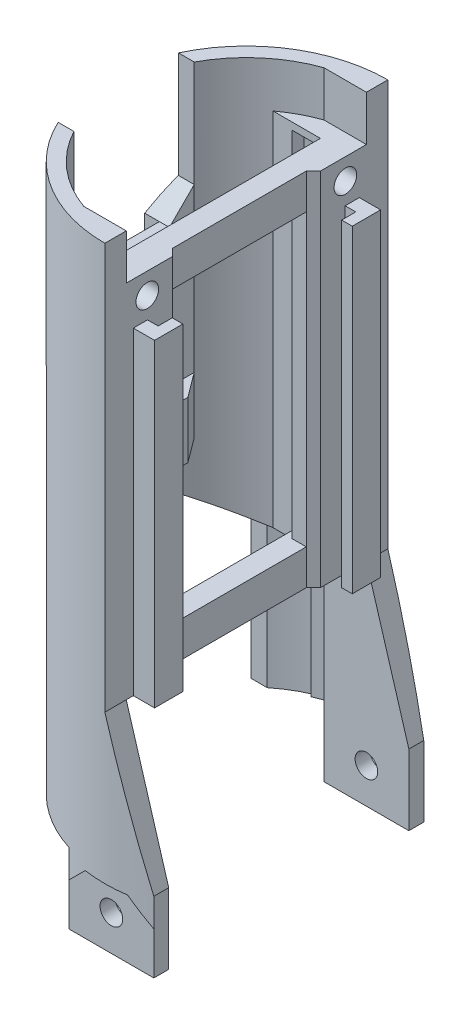
SolidWorks part; units mm, degrees
ref_plane "前视基准面" through (0, 0, 0) normal (0, 0, 1) x (1, 0, 0)
ref_plane "上视基准面" through (0, 0, 0) normal (0, 1, 0) x (1, 0, 0)
ref_plane "右视基准面" through (0, 0, 0) normal (1, 0, 0) x (0, 0, -1)
other "Configuration Table"
sketch "草图1" plane through (0, 0, 0) normal (0, 1, 0) x (1, 0, 0)
  line L0 (0, -473.638) -> (0, 23208.2609) construction
  line L1 (0, 0) -> (-4, 0) construction
  line L2 (0, 20) -> (0, -20)
  line L3 (-4, -17.5499) -> (-4, 17.5499)
  arc A0 (0, 20) -> (0, -20) centre (0, 0) ccw
  arc A1 (-4, 17.5499) -> (-4, -17.5499) centre (0, 0) ccw
  point P12 (-4, 0)
  dimension "D1" = 40
  dimension "D2" = 36
  dimension "D3" = 4
extrude "凸台-拉伸1" add sketch "草图1" along normal blind 70
sketch "草图3" plane through (0, 0, 0) normal (1, 0, 0) x (0, 0, -1)
  line L0 (-20, 0) -> (20, 0) construction
  line L1 (-16, 60) -> (16, 60) construction
  line L2 (-16, 60) -> (-16, 0) construction
  line L3 (-16, 0) -> (16, 0) construction
  line L4 (16, 60) -> (16, 0) construction
  line L5 (-20, 70) -> (20, 70) construction
  circle A0 centre (-14, 58) radius 2 construction
  circle A1 centre (14, 58) radius 2 construction
  circle A2 centre (-14, 58) radius 1
  circle A3 centre (14, 58) radius 1
  point P4 (0, 60)
  dimension "D4" = 4
  dimension "D5" = 4
  dimension "D6" = 2
  dimension "D7" = 2
  dimension "D1" = 0
  dimension "D2" = 10
  dimension "D3" = 32
extrude "切除-拉伸2" cut sketch "草图3" against normal up to surface (4 mm away) from surface up to face at (-4, 35, 0) starting at face at (0, 35, 0)
sketch "草图5" plane through (0, 0, 0) normal (0, 1, 0) x (1, 0, 0)
  line L0 (0, -1000) -> (0, 49000) construction
  line L1 (-1000, 0) -> (49000, 0) construction
  line L2 (-6, 16.9706) -> (6, 16.9706) construction
  line L3 (-6, -16.9706) -> (6, -16.9706) construction
  line L4 (0, 16.9706) -> (0, -16.9706)
  line L5 (0, -16.9706) -> (-4, -16.9706)
  line L6 (-4, -17.5499) -> (-4, 17.5499) construction
  line L7 (-4, -16.9706) -> (-4, 16.9706)
  line L8 (-4, 16.9706) -> (0, 16.9706)
  circle A0 centre (0, 0) radius 18 construction
  point P11 (0, 16.9706)
  dimension "D1" = 12
extrude "切除-拉伸4" cut sketch "草图5" against normal blind 9 from surface starting at face at (-10, 70, 0)
sketch "草图6" plane through (0, 0, 0) normal (0, 1, 0) x (1, 0, 0)
  line L0 (-4, 16.9706) -> (-6, 16.9706)
  line L1 (0, 16.9706) -> (0, 18)
  line L2 (-4, -16.9706) -> (-6, -16.9706)
  line L3 (0, -16.9706) -> (0, -18)
  line L4 (-4, 16.9706) -> (-4, -16.9706)
  line L5 (0, 16.9706) -> (-4, 16.9706)
  line L6 (0, -16.9706) -> (0, 16.9706)
  line L7 (-4, -16.9706) -> (0, -16.9706)
  line L9 (0, 16.9706) -> (-4, 16.9706)
  line L11 (-4, -16.9706) -> (0, -16.9706)
  arc A0 (0, 18) -> (-6, 16.9706) centre (0, 0) ccw
  arc A1 (-6, -16.9706) -> (0, -18) centre (0, 0) ccw
  dimension "D1" = 0
extrude "凸台-拉伸2" add sketch "草图6" against normal up to surface from surface up to face at (-10, 0, 0) starting at face at (-6.25, 70, 0)
sketch "草图7" plane through (0, 0, 0) normal (0, 1, 0) x (1, 0, 0)
  line L4 (-4, 16.9706) -> (-4, -16.9706)
  line L5 (0, 16.9706) -> (-4, 16.9706)
  line L6 (0, -16.9706) -> (0, 16.9706)
  line L7 (-4, -16.9706) -> (0, -16.9706)
  line L8 (-4, 16.9706) -> (-4, -16.9706)
  line L9 (0, 16.9706) -> (-4, 16.9706)
  line L10 (0, -16.9706) -> (0, 16.9706)
  line L11 (-4, -16.9706) -> (0, -16.9706)
  dimension "D1" = 0
extrude "切除-拉伸5" cut sketch "草图7" along normal blind 10
sketch "草图8" plane through (0, 0, 0) normal (0, 1, 0) x (1, 0, 0)
  line L0 (0, 16.9706) -> (0, -16.9706) construction
  line L1 (-6, 16.9706) -> (0, 16.9706)
  line L2 (-6, 16.9706) -> (-6, 14.4706)
  line L3 (-6, 14.4706) -> (0, 14.4706)
  line L4 (0, 16.9706) -> (0, 14.4706)
  line L6 (0, -16.9706) -> (-6, -16.9706)
  line L7 (0, -16.9706) -> (0, -14.4706)
  line L8 (0, -14.4706) -> (-6, -14.4706)
  line L9 (-6, -16.9706) -> (-6, -14.4706)
  dimension "D1" = 2.5
  dimension "D2" = 2.5
extrude "凸台-拉伸3" add sketch "草图8" against normal blind 1 from surface starting at face at (-2, 61, 0)
sketch "草图10" plane through (0, 0, 0) normal (0, 1, 0) x (1, 0, 0)
  line L0 (-6, 16.9706) -> (-6, 14.4706)
  line L1 (-6, 14.4706) -> (-10.7053, 14.4706)
  line L2 (-6, -14.4706) -> (-10.7053, -14.4706)
  line L3 (-6, -14.4706) -> (-6, -16.9706)
  arc A0 (-6, 16.9706) -> (-10.7053, 14.4706) centre (0, 0) ccw
  arc A1 (-10.7053, -14.4706) -> (-6, -16.9706) centre (0, 0) ccw
extrude "凸台-拉伸4" add sketch "草图10" along normal up to surface (70 mm away) from surface up to face at (-7.3333, 70, 0) starting at face at (-7.3333, 0, 0)
sketch "草图11" plane through (0, 0, 0) normal (0, 1, 0) x (1, 0, 0)
  line L0 (0, 16.9706) -> (0, -16.9706) construction
  line L1 (-6, 16.9706) -> (0, 16.9706)
  line L2 (-6, 16.9706) -> (-6, 14.4706)
  line L3 (-6, 14.4706) -> (0, 14.4706)
  line L4 (0, 16.9706) -> (0, 14.4706)
  line L5 (-6, 14.4706) -> (-10.7053, 14.4706) construction
  line L7 (-6, -14.4706) -> (0, -14.4706)
  line L8 (-6, -14.4706) -> (-6, -16.9706)
  line L9 (-6, -16.9706) -> (0, -16.9706)
  line L10 (0, -14.4706) -> (0, -16.9706)
  dimension "D1" = 0
extrude "凸台-拉伸5" add sketch "草图11" along normal up to surface (70 mm away) from surface up to face at (-7.2705, 70, 0) starting at face at (-4, 61, 0)
sketch "草图12" plane through (0, 0, 0) normal (0, 0, 1) x (1, 0, 0)
  line L1 (-6, 60) -> (-4, 60)
  line L2 (-6, 60) -> (-6, 61)
  line L3 (-6, 61) -> (-4, 61)
  line L4 (-4, 60) -> (-4, 61)
extrude "切除-拉伸6" cut sketch "草图12" against normal up to surface (16.9706 mm away) from surface up to face at (-3.3333, 23.3333, -16.9706) starting at face at (-3.3333, 23.3333, 16.9706)
sketch "草图14" plane through (0, 0, 0) normal (0, 1, 0) x (1, 0, 0)
  line L0 (-4, -14.4706) -> (-4, 14.4706) construction
  line L1 (-4, 10.4706) -> (-3, 10.4706)
  line L2 (-4, 10.4706) -> (-4, -10.4706)
  line L3 (-4, -10.4706) -> (-3, -10.4706)
  line L4 (-3, 10.4706) -> (-3, -10.4706)
  line L5 (-10.7053, -14.4706) -> (0, -14.4706) construction
  line L6 (-4, 14.4706) -> (0, 14.4706) construction
  line L7 (0, 14.4706) -> (0, -14.4706) construction
  line L8 (-1, 10.4706) -> (0, 10.4706)
  line L9 (-1, 10.4706) -> (-1, -10.4706)
  line L10 (-1, -10.4706) -> (0, -10.4706)
  line L11 (0, 10.4706) -> (0, -10.4706)
  line L12 (0, -14.4706) -> (-4, -14.4706) construction
  line L13 (0, 14.4706) -> (-10.7053, 14.4706) construction
  dimension "D1" = 1
  dimension "D2" = 4
  dimension "D3" = 4
  dimension "D4" = 1
  dimension "D5" = 4
  dimension "D6" = 4
extrude "切除-拉伸8" cut sketch "草图14" along normal up to surface (61 mm away) from surface up to face at (-2, 61, 0) starting at face at (-2, 10, 0)
sketch "草图15" plane through (0, 0, 0) normal (1, 0, 0) x (0, 0, -1)
  line L0 (10.4706, 61) -> (10.4706, 10) construction
  line L5 (-10.4706, 61) -> (-10.4706, 10) construction
  line L6 (10.4706, 61) -> (-10.4706, 61) construction
  line L7 (-10.4706, 10) -> (10.4706, 10) construction
  line L9 (-9.4706, 56) -> (9.4706, 56)
  line L10 (-9.4706, 56) -> (-9.4706, 15)
  line L11 (-9.4706, 15) -> (9.4706, 15)
  line L12 (9.4706, 56) -> (9.4706, 15)
  dimension "D1" = 1
  dimension "D2" = 1
  dimension "D3" = 5
  dimension "D4" = 5
extrude "切除-拉伸9" cut sketch "草图15" against normal up to surface (3 mm away) from surface up to face at (-3, 35.5, 0) starting at face at (-1, 35.5, 0)
sketch "草图17" plane through (0, 0, 0) normal (1, 0, 0) x (0, 0, -1)
  circle A0 centre (-14, 58) radius 1.6
  circle A1 centre (14, 58) radius 1.6
  dimension "D1" = 3.2
  dimension "D2" = 3.2
extrude "切除-拉伸10" cut sketch "草图17" against normal blind 2.5
sketch "草图20" plane through (0, 0, 0) normal (0, 1, 0) x (1, 0, 0)
  line L0 (-1, 10.4706) -> (0, 10.4706)
  line L1 (0, 14.4706) -> (0, 10.4706) construction
  line L2 (0, 10.4706) -> (-1, 10.4706) construction
  line L3 (0, 10.4706) -> (-1, 9.4706)
  line L4 (-1, 10.4706) -> (-1, -10.4706) construction
  line L5 (-1, 9.4706) -> (-1, 10.4706)
  line L6 (-4, 10.4706) -> (-3, 10.4706)
  line L7 (-3, 10.4706) -> (-3, 9.4706)
  line L8 (-3, -10.4706) -> (-3, 10.4706) construction
  line L9 (-3, 9.4706) -> (-4, 10.4706)
  line L10 (-4, -10.4706) -> (-3, -10.4706)
  line L11 (-3, -10.4706) -> (-3, -9.4706)
  line L12 (-3, -9.4706) -> (-4, -10.4706)
  line L13 (0, -10.4706) -> (-1, -10.4706)
  line L14 (-1, -10.4706) -> (0, -10.4706) construction
  line L15 (-1, -10.4706) -> (-1, -9.4706)
  line L16 (-1, -9.4706) -> (0, -10.4706)
  dimension "D1" = 1
  dimension "D2" = 1
  dimension "D3" = 1
  dimension "D4" = 1
  dimension "D5" = 1
extrude "凸台-拉伸11" add sketch "草图20" against normal up to surface (-10 mm away) from surface up to face at (-2, 10, 0) starting at face at (-2, 61, 0)
sketch "草图21" plane through (0, 0, 0) normal (0, 1, 0) x (1, 0, 0)
  line L0 (-4, 10.4706) -> (-4, -10.4706)
  line L1 (-4, -10.4706) -> (-3, -9.4706)
  line L2 (-3, -9.4706) -> (-3, 9.4706)
  line L3 (-3, 9.4706) -> (-4, 10.4706)
extrude "凸台-拉伸12" add sketch "草图21" against normal up to surface (-56 mm away) from surface up to face at (-2, 56, 0) starting at face at (-2, 61, 0)
sketch "草图22" plane through (0, 0, 0) normal (0, 1, 0) x (1, 0, 0)
  line L4 (-4, 10.4706) -> (-4, -10.4706)
  line L5 (-4, -10.4706) -> (-3, -9.4706)
  line L6 (-3, -9.4706) -> (-3, 9.4706)
  line L7 (-3, 9.4706) -> (-4, 10.4706)
  line L8 (-4, 10.4706) -> (-4, -10.4706)
  line L9 (-4, -10.4706) -> (-3, -9.4706)
  line L10 (-3, -9.4706) -> (-3, 9.4706)
  line L11 (-3, 9.4706) -> (-4, 10.4706)
  dimension "D1" = 0
extrude "凸台-拉伸13" add sketch "草图22" along normal up to surface (15 mm away) from surface up to face at (-2, 15, 0) starting at face at (-2, 10, 0)
sketch "草图23" plane through (0, 0, 0) normal (0, 0, 1) x (1, 0, 0)
  line L0 (-3, 56) -> (-1, 56) construction
  line L1 (-6, 61) -> (-8, 61)
  line L2 (-6, 61) -> (-6, 55)
  line L3 (-6, 55) -> (-8, 55)
  line L4 (-8, 61) -> (-8, 55)
  dimension "D1" = 1
  dimension "D2" = 2
extrude "切除-拉伸11" cut sketch "草图23" along normal up to surface (1.654 mm away) from surface up to face at (-14.3526, 35, 0) starting at face at (-5.3444, 46.1429, 14.4706)
sketch "草图24" plane through (0, 0, 0) normal (0, 0, 1) x (1, 0, 0)
  line L4 (-6, 61) -> (-8, 61)
  line L5 (-8, 61) -> (-8, 55)
  line L6 (-8, 55) -> (-6, 55)
  line L7 (-6, 55) -> (-6, 61)
  line L8 (-6, 61) -> (-8, 61)
  line L9 (-8, 61) -> (-8, 55)
  line L10 (-8, 55) -> (-6, 55)
  line L11 (-6, 55) -> (-6, 61)
  dimension "D1" = 0
extrude "切除-拉伸12" cut sketch "草图24" against normal up to surface (16.1245 mm away) up to face at (-14.3526, 35, 0)
sketch "草图25" plane through (0, 0, 0) normal (0, 1, 0) x (1, 0, 0)
  line L0 (-6, -16.9706) -> (-6, -14.4706)
  line L1 (-8, -14.4706) -> (-4, -14.4706) construction
  line L2 (-6, -14.4706) -> (-10.7053, -14.4706)
  line L3 (-10.7053, 14.4706) -> (-6, 14.4706)
  line L4 (-4, 14.4706) -> (-8, 14.4706) construction
  line L5 (-6, 14.4706) -> (-6, 16.9706)
  arc A0 (-10.7053, -14.4706) -> (-6, -16.9706) centre (0, 0) ccw
  arc A1 (-6, 16.9706) -> (-10.7053, 14.4706) centre (0, 0) ccw
extrude "切除-拉伸13" cut sketch "草图25" along normal up to surface (10 mm away) from surface up to face at (-1.25, 10, 0) starting at face at (-7.2705, 0, 0)
sketch "草图26" plane through (0, 0, 0) normal (1, 0, 0) x (0, 0, -1)
  line L0 (-14.4706, 55) -> (-14.4706, 10) construction
  line L1 (14.4706, 55) -> (14.4706, 10) construction
  line L2 (-14.4706, 55) -> (-14.4706, 10) construction
  line L3 (14.4706, 55) -> (14.4706, 10) construction
  line L4 (-16.9706, 0) -> (16.9706, 0) construction
  line L5 (14.4706, 10) -> (-14.4706, 10) construction
  line L6 (14.4706, 10) -> (14.4706, 15) construction
  line L7 (14.4706, 15) -> (-14.4706, 15) construction
  line L8 (-14.4706, 10) -> (-14.4706, 15) construction
  line L9 (-14.4706, 10) -> (14.4706, 10) construction
  line L10 (-14.4706, 10) -> (-14.4706, 0)
  line L11 (-14.4706, 0) -> (14.4706, 0)
  line L12 (14.4706, 10) -> (14.4706, 0)
  line L13 (-14.4706, 10) -> (-6.9706, 15)
  line L14 (14.4706, 10) -> (6.9706, 15)
  line L15 (-6.9706, 15) -> (6.9706, 15)
  dimension "D1" = 5
  dimension "D2" = 7.5
  dimension "D3" = 7.5
extrude "切除-拉伸17" cut sketch "草图26" against normal up to surface (13.8059 mm away) from surface up to face at (-10, 35, 0) starting at face at (-4, 44, 0)
sketch "草图29" plane through (0, 0, 0) normal (0, 1, 0) x (1, 0, 0)
  line L0 (0, -16.9706) -> (0, -14.4706)
  line L1 (0, -14.4706) -> (-10.7053, -14.4706)
  line L2 (0, -16.9706) -> (-6, -16.9706)
  line L3 (-4, -16.9706) -> (-6, -16.9706)
  line L4 (0, -18) -> (0, -16.9706)
  line L5 (0, -16.9706) -> (-4, -16.9706)
  line L6 (-4, -16.9706) -> (-6, -16.9706) construction
  line L8 (0, -16.9706) -> (-4, -16.9706) construction
  line L9 (-6, 16.9706) -> (-4, 16.9706)
  line L10 (0, 16.9706) -> (0, 18)
  line L11 (-4, 16.9706) -> (0, 16.9706)
  line L12 (-6, 16.9706) -> (-4, 16.9706) construction
  line L14 (-4, 16.9706) -> (0, 16.9706) construction
  line L15 (-6, 16.9706) -> (0, 16.9706)
  line L16 (0, 16.9706) -> (0, 14.4706)
  line L17 (0, 14.4706) -> (-10.7053, 14.4706)
  arc A0 (-10.7053, -14.4706) -> (-6, -16.9706) centre (0, 0) ccw
  arc A1 (-6, -16.9706) -> (0, -18) centre (0, 0) ccw
  arc A3 (0, 18) -> (-6, 16.9706) centre (0, 0) ccw
  arc A5 (-6, 16.9706) -> (-10.7053, 14.4706) centre (0, 0) ccw
  dimension "D1" = 0
  dimension "D2" = 0
extrude "切除-拉伸18" cut sketch "草图29" against normal up to surface (-61 mm away) from surface up to face at (-1.25, 61, 0) starting at face at (-8.1175, 70, 0)
sketch "草图30" plane through (0, 0, 0) normal (0, 1, 0) x (1, 0, 0)
  line L0 (-8, 16.1245) -> (-8, 14.4706)
  line L1 (-8, 14.4706) -> (-4, 14.4706)
  line L2 (-4, -16.9706) -> (-4, 16.9706) construction
  line L3 (-4, 14.4706) -> (-4, 16.9706)
  line L4 (-6, 16.9706) -> (0, 16.9706) construction
  line L5 (-4, 16.9706) -> (-6, 16.9706)
  line L6 (-8, -16.1245) -> (-8, -14.4706)
  line L7 (-8, -14.4706) -> (-4, -14.4706)
  line L8 (-4, -14.4706) -> (-4, -16.9706)
  line L9 (-4, -16.9706) -> (-6, -16.9706)
  arc A0 (-6, 16.9706) -> (-8, 16.1245) centre (0, 0) ccw
  arc A1 (-8, -16.1245) -> (-6, -16.9706) centre (0, 0) ccw
extrude "凸台-拉伸16" add sketch "草图30" against normal blind 1 from surface starting at face at (-8.9139, 61, -15.0418)
sketch "草图31" plane through (0, 0, 0) normal (0, 1, 0) x (1, 0, 0)
  line L4 (0, -20) -> (0, -16.9706)
  line L5 (0, -16.9706) -> (-6, -16.9706)
  line L6 (-6, 16.9706) -> (0, 16.9706)
  line L7 (0, 16.9706) -> (0, 20)
  line L8 (0, -20) -> (0, -16.9706)
  line L9 (0, -16.9706) -> (-6, -16.9706)
  line L10 (-6, 16.9706) -> (0, 16.9706)
  line L11 (0, 16.9706) -> (0, 20)
  arc A2 (-6, 16.9706) -> (-6, -16.9706) centre (0, 0) ccw
  arc A3 (0, 20) -> (0, -20) centre (0, 0) ccw
  arc A4 (-6, 16.9706) -> (-6, -16.9706) centre (0, 0) ccw
  arc A5 (0, 20) -> (0, -20) centre (0, 0) ccw
  dimension "D1" = 0
extrude "凸台-拉伸17" add sketch "草图31" along normal blind 2.4 from surface starting at face at (-7.3333, 70, 0)
sketch "草图32" plane through (0, 0, 0) normal (0, 1, 0) x (1, 0, 0)
  line L4 (0, 16.9706) -> (0, 20)
  line L5 (0, -20) -> (0, -16.9706)
  line L6 (0, -16.9706) -> (-6, -16.9706)
  line L7 (-6, 16.9706) -> (0, 16.9706)
  line L8 (0, 16.9706) -> (0, 20)
  line L9 (0, -20) -> (0, -16.9706)
  line L10 (0, -16.9706) -> (-6, -16.9706)
  line L11 (-6, 16.9706) -> (0, 16.9706)
  arc A2 (0, 20) -> (0, -20) centre (0, 0) ccw
  arc A3 (-6, 16.9706) -> (-6, -16.9706) centre (0, 0) ccw
  arc A4 (0, 20) -> (0, -20) centre (0, 0) ccw
  arc A5 (-6, 16.9706) -> (-6, -16.9706) centre (0, 0) ccw
  dimension "D1" = 0
extrude "切除-拉伸19" cut sketch "草图32" against normal blind 5 from surface starting at face at (-7.3333, 72.4, 0)
sketch "草图33" plane through (0, 0, 0) normal (0, 1, 0) x (1, 0, 0)
  line L0 (-1000, 0) -> (49000, 0) construction
  line L1 (-17.2916, -5) -> (-17.2916, 5)
  line L2 (-17.2916, 5) -> (-19.3649, 5)
  line L3 (-17.2916, -5) -> (-19.3649, -5)
  arc A0 (-17.2916, 5) -> (-17.2916, -5) centre (0, 0) ccw construction
  arc A1 (-19.3649, 5) -> (-19.3649, -5) centre (0, 0) ccw
  point P11 (-17.2916, 0)
  dimension "D1" = 10
extrude "切除-拉伸20" cut sketch "草图33" against normal blind 45 from surface starting at face at (-7.3333, 67.4, 0)
sketch "草图39" plane through (0, 0, 0) normal (0, 1, 0) x (1, 0, 0)
  line L0 (-20, 0) -> (-15.8666, 0) construction
  line L1 (-15.8666, -8.5) -> (-15.8666, 8.5)
  line L2 (-15.8666, 8.5) -> (-18.1039, 8.5)
  line L3 (-15.8666, -8.5) -> (-18.1039, -8.5)
  arc A0 (-18.1039, 8.5) -> (-18.1039, -8.5) centre (0, 0) ccw
  arc A1 (-15.8666, 8.5) -> (-15.8666, -8.5) centre (0, 0) ccw construction
  point P11 (-15.8666, 0)
  dimension "D1" = 17
extrude "切除-拉伸22" cut sketch "草图39" against normal blind 15 from surface contours L2 A0 L3 L1 region at (-17.6683, 0, 0) starting at face at (-9.3339, 67.4, 13.7237)
sketch "草图40" plane through (0, 0, 0) normal (1, 0, 0) x (0, 0, -1)
  line L0 (-5, 52.4) -> (-8.5, 52.4)
  line L1 (-8.5, 52.4) -> (-5, 48.9)
  line L2 (-5, 22.4) -> (-5, 52.4) construction
  line L3 (-5, 48.9) -> (-5, 52.4)
  line L4 (8.5, 52.4) -> (5, 52.4)
  line L5 (5, 52.4) -> (5, 48.9)
  line L6 (5, 22.4) -> (5, 52.4) construction
  line L7 (5, 48.9) -> (8.5, 52.4)
  dimension "D1" = 3.5
  dimension "D2" = 3.5
extrude "切除-拉伸25" cut sketch "草图40" against normal through all
sketch "草图41" plane through (0, 0, 0) normal (0, 1, 0) x (1, 0, 0)
  line L0 (-1000, 0) -> (49000, 0) construction
  line L1 (-15.8666, 8.5) -> (-15.8666, -8.5)
  line L2 (-17.2916, 5) -> (-17.2916, -5)
  arc A0 (-17.2916, -5) -> (-15.8666, -8.5) centre (0, 0) ccw
  arc A1 (-15.8666, 8.5) -> (-17.2916, 5) centre (0, 0) ccw
extrude "凸台-拉伸24" add sketch "草图41" along normal up to vertex from surface up to point (-19.3649, 48.9, -5) starting at face at (-18.6641, 22.4, 0)
sketch "草图42" plane through (0, 0, 0) normal (1, 0, 0) x (0, 0, -1)
  line L0 (-8.5, 52.4) -> (-8.5, 48.9)
  line L1 (-8.5, 48.9) -> (-5, 48.9)
  line L2 (-5, 48.9) -> (-8.5, 52.4)
  line L3 (8.5, 52.4) -> (8.5, 48.9)
  line L4 (8.5, 48.9) -> (5, 48.9)
  line L5 (5, 48.9) -> (8.5, 52.4)
extrude "凸台-拉伸25" add sketch "草图42" against normal up to surface (2.2372 mm away) from surface up to face at (-13.8836, 31.4825, 0) starting at face at (-15.8666, 35.65, 0)
sketch "草图43" plane through (0, 0, 0) normal (0, 1, 0) x (1, 0, 0)
  line L0 (-15.8666, 8.5) -> (-15.8666, -8.5)
  arc A0 (-15.8666, 8.5) -> (-15.8666, -8.5) centre (0, 0) ccw
extrude "凸台-拉伸26" add sketch "草图43" against normal blind 1 from surface starting at face at (-16.6252, 22.4, 0)
sketch "草图44" plane through (0, 0, 0) normal (0, 1, 0) x (1, 0, 0)
  line L0 (-1000, 0) -> (49000, 0) construction
  line L1 (-15.8666, 0) -> (-13.2666, 0) construction
  line L2 (-15.8666, 5) -> (-15.8666, -5) construction
  line L3 (-13.2666, -5) -> (-13.2666, 5)
  line L4 (-13.2666, 5) -> (-15.8666, 8.5)
  line L5 (-13.2666, -5) -> (-15.8666, -8.5)
  line L6 (-15.8666, 8.5) -> (-15.8666, -8.5)
  circle A1 centre (0, 0) radius 18 construction
  point P12 (-13.2666, 0)
  dimension "D1" = 2.6
  dimension "D2" = 10
extrude "凸台-拉伸27" add sketch "草图44" along normal blind 8 from surface starting at face at (-16.9333, 21.4, 0)
sketch "草图45" plane through (0, 0, 0) normal (1, 0, 0) x (0, 0, -1)
  line L0 (0, 67.4) -> (0, 21.4) construction
  line L2 (5, 22.4) -> (-5, 22.4) construction
  circle A0 centre (0, 26.4) radius 1
  dimension "D1" = 2
  dimension "D2" = 4
extrude "切除-拉伸26" cut sketch "草图45" along normal up to surface (13.2666 mm away) from surface up to face at (-13.2666, 25.4, 0) starting at face at (-17.2916, 35.65, 0)
sketch "草图46" plane through (0, 0, 0) normal (0, 1, 0) x (1, 0, 0)
  line L0 (-15.8666, 5) -> (-15.8666, -5) construction
  line L1 (-15.8666, 2) -> (-14.2666, 2)
  line L2 (-15.8666, 2) -> (-15.8666, -2)
  line L3 (-15.8666, -2) -> (-14.2666, -2)
  line L4 (-14.2666, 2) -> (-14.2666, -2)
  line L5 (-17.2916, -5) -> (-17.2916, 5) construction
  point P8 (-17.2916, 0)
  point P9 (-15.8666, 0)
  dimension "D1" = 4
  dimension "D2" = 1.6
extrude "切除-拉伸27" cut sketch "草图46" along normal blind 5 from surface starting at face at (-15.1, 21.4, 0)
sketch "草图47" plane through (0, 0, 0) normal (1, 0, 0) x (0, 0, -1)
  line L1 (0, 24.0906) -> (2, 25.2453)
  line L2 (2, 25.2453) -> (2, 27.5547)
  line L3 (2, 27.5547) -> (0, 28.7094)
  line L4 (0, 28.7094) -> (-2, 27.5547)
  line L5 (-2, 27.5547) -> (-2, 25.2453)
  line L6 (-2, 25.2453) -> (0, 24.0906)
  circle A0 centre (0, 26.4) radius 2 construction
  dimension "D1" = 4
extrude "切除-拉伸28" cut sketch "草图47" against normal up to surface (1.6 mm away) from surface up to face at (-15.8666, 24.5667, 0) starting at face at (-14.2666, 24.5667, 0)
sketch "草图48" plane through (0, 0, 0) normal (1, 0, 0) x (0, 0, -1)
  line L0 (5, 22.4) -> (3, 22.4)
  line L1 (5, 22.4) -> (-5, 22.4) construction
  line L2 (3, 22.4) -> (5, 24.4)
  line L3 (5, 22.4) -> (5, 48.9) construction
  line L4 (5, 24.4) -> (5, 22.4)
  line L5 (-5, 22.4) -> (-5, 24.4)
  line L6 (-5, 22.4) -> (-5, 48.9) construction
  line L7 (-5, 24.4) -> (-3, 22.4)
  line L8 (-3, 22.4) -> (-5, 22.4)
  dimension "D1" = 2
  dimension "D2" = 2
  dimension "D3" = 2
  dimension "D4" = 2
extrude "凸台-拉伸28" add sketch "草图48" against normal up to surface (2.0733 mm away) from surface up to face at (-13.8836, 31.4825, 0) starting at face at (-17.2916, 26.4, 1)
sketch "草图49" plane through (0, 0, 0) normal (0, 1, 0) x (1, 0, 0)
  line L0 (0, -16.9706) -> (0, -15.9706) construction
  line L1 (0, -16.9706) -> (0, -10.4706) construction
  line L2 (0, -15.9706) -> (3, -15.9706)
  line L3 (3, -15.9706) -> (3, -11.9706)
  line L5 (1.5, -11.9706) -> (1.5, -13.9706)
  line L6 (1.5, -13.9706) -> (0, -13.9706)
  line L7 (0, -13.9706) -> (0, -15.9706)
  line L8 (-1000, 0) -> (49000, 0) construction
  line L9 (0, 16.9706) -> (0, 15.9706) construction
  line L10 (0, 13.9706) -> (0, 15.9706)
  line L11 (1.5, 13.9706) -> (0, 13.9706)
  line L12 (1.5, 11.9706) -> (1.5, 13.9706)
  line L13 (3, 11.9706) -> (1.5, 11.9706)
  line L14 (3, 15.9706) -> (3, 11.9706)
  line L15 (0, 15.9706) -> (3, 15.9706)
  line L16 (3, -11.9706) -> (1.5, -11.9706)
  dimension "D1" = 1
  dimension "D2" = 4
  dimension "D3" = 3
  dimension "D4" = 1.5
  dimension "D5" = 2
extrude "凸台-拉伸29" add sketch "草图49" along normal blind 45 from surface starting at face at (-1.25, 10, 0)
sketch "草图51" plane through (0, 0, 0) normal (0, 1, 0) x (1, 0, 0)
  line L0 (-10.7053, 14.4706) -> (-13.8059, 14.4706) construction
  line L1 (0, 20) -> (0, 16.9706) construction
  line L2 (0, 16.9706) -> (-6, 16.9706) construction
  line L3 (-13.8059, -14.4706) -> (-10.7053, -14.4706) construction
  line L4 (-6, -16.9706) -> (0, -16.9706) construction
  line L5 (0, -16.9706) -> (0, -20) construction
  line L6 (-10.7053, 14.4706) -> (-13.8059, 14.4706)
  line L7 (0, 20) -> (0, 16.9706)
  line L8 (0, 16.9706) -> (-6, 16.9706)
  line L9 (-13.8059, -14.4706) -> (-10.7053, -14.4706)
  line L10 (-6, -16.9706) -> (0, -16.9706)
  line L11 (0, -16.9706) -> (0, -20)
  arc A0 (0, 20) -> (-13.8059, 14.4706) centre (0, 0) ccw construction
  arc A1 (-6, 16.9706) -> (-10.7053, 14.4706) centre (0, 0) ccw construction
  arc A2 (-10.7053, -14.4706) -> (-6, -16.9706) centre (0, 0) ccw construction
  arc A3 (-13.8059, -14.4706) -> (0, -20) centre (0, 0) ccw construction
  arc A4 (0, 20) -> (-13.8059, 14.4706) centre (0, 0) ccw
  arc A5 (-6, 16.9706) -> (-10.7053, 14.4706) centre (0, 0) ccw
  arc A6 (-10.7053, -14.4706) -> (-6, -16.9706) centre (0, 0) ccw
  arc A7 (-13.8059, -14.4706) -> (0, -20) centre (0, 0) ccw
extrude "凸台-拉伸30" add sketch "草图51" against normal blind 10
sketch "草图62" plane through (0, 0, 0) normal (0, 1, 0) x (1, 0, 0)
  line L1 (0, 20) -> (0, 16.9706) construction
  line L2 (0, 16.9706) -> (-6, 16.9706) construction
  line L4 (-6, -16.9706) -> (0, -16.9706) construction
  line L5 (0, -16.9706) -> (0, -20) construction
  line L7 (0, 20) -> (0, 16.9706) construction
  line L8 (6, 16.9706) -> (-6, 16.9706)
  line L10 (-6, -16.9706) -> (6, -16.9706)
  line L11 (0, -16.9706) -> (0, -20) construction
  line L12 (-6, -16.9706) -> (-6, -19.0788)
  line L13 (-6, 16.9706) -> (-6, 19.0788)
  line L14 (0, -1000) -> (0, 49000) construction
  line L15 (6, 16.9706) -> (6, 19.0788)
  line L16 (6, -16.9706) -> (6, -19.0788)
  arc A1 (0, 20) -> (-13.8059, 14.4706) centre (0, 0) ccw construction
  arc A2 (-13.8059, -14.4706) -> (0, -20) centre (0, 0) ccw construction
  arc A5 (6, 19.0788) -> (-6, 19.0788) centre (0, 0) ccw
  arc A6 (-6, -19.0788) -> (6, -19.0788) centre (0, 0) ccw
extrude "凸台-拉伸34" add sketch "草图62" along normal blind 20 and the other way blind 10 from surface starting at face at (-6.2275, -10, -16.8777)
sketch "草图64" plane through (0, 0, 0) normal (0, 0, 1) x (1, 0, 0)
  line L0 (0, 10) -> (6, -10)
  line L1 (6, -20) -> (6, 10) construction
  line L2 (6, -10) -> (6, 10)
  line L3 (6, 10) -> (0, 10)
extrude "切除-拉伸38" cut sketch "草图64" against normal through all and the other way through all
sketch "草图66" plane through (0, 0, 0) normal (0, 1, 0) x (1, 0, 0)
  line L0 (-6, -19.0788) -> (6, -19.0788)
  line L1 (-6, 19.0788) -> (6, 19.0788)
  arc A0 (-6, -19.0788) -> (6, -19.0788) centre (0, 0) ccw construction
  arc A1 (-6, -19.0788) -> (6, -19.0788) centre (0, 0) ccw
  arc A2 (6, 19.0788) -> (-6, 19.0788) centre (0, 0) ccw construction
  arc A3 (6, 19.0788) -> (-6, 19.0788) centre (0, 0) ccw
extrude "切除-拉伸39" cut sketch "草图66" along normal blind 10 from surface starting at face at (0, -20, 18.255)
sketch "草图68" plane through (0, 0, 0) normal (0, 0, 1) x (1, 0, 0)
  line L0 (6, -20) -> (-6, -20) construction
  line L1 (6, -20) -> (6, -10) construction
  circle A0 centre (0, -15) radius 1.6
  dimension "D1" = 3.2
  dimension "D2" = 5
  dimension "D3" = 6
extrude "切除-拉伸40" cut sketch "草图68" against normal through all and the other way through all
sketch "草图69" plane through (0, 0, 0) normal (0, 0, 1) x (1, 0, 0)
  line L0 (6, -10) -> (6, -14)
  line L3 (6, -20) -> (6, -10) construction
  line L6 (6, -10) -> (-6, -10)
  line L10 (6, -14) -> (3, -11)
  line L11 (3, -11) -> (-3, -11)
  line L12 (-3, -11) -> (-6, -14)
  line L13 (-6, -20) -> (-6, -10) construction
  line L14 (-6, -14) -> (-6, -10)
  point P14 (6, -11.5552)
  dimension "D1" = 4
  dimension "D2" = 4
  dimension "D3" = 6
  dimension "D4" = 3
  dimension "D5" = 3
extrude "凸台-拉伸35" add sketch "草图69" along normal up to surface from surface up to face at (-12.0203, 23.9692, 0) starting at face at (1.6, -15, 19.0788)
sketch "草图70" plane through (0, 0, 0) normal (0, 0, 1) x (1, 0, 0)
  line L6 (-6, -10) -> (-6, -14)
  line L7 (-6, -10) -> (-6, -14)
  line L8 (-6, -14) -> (-3, -11)
  line L9 (6, -10) -> (-6, -10)
  line L10 (-6, -14) -> (-3, -11)
  line L11 (-3, -11) -> (3, -11)
  line L15 (6, -10) -> (-6, -10)
  line L18 (-3, -11) -> (3, -11)
  line L19 (3, -11) -> (6, -14)
  line L20 (3, -11) -> (6, -14)
  line L21 (6, -14) -> (6, -10)
  line L22 (6, -14) -> (6, -10)
  dimension "D1" = 0
extrude "凸台-拉伸36" add sketch "草图70" against normal up to surface from surface up to face at (-10.3031, 18.7583, 2.7545) starting at face at (-1.6, -15, -19.0788)
sketch "草图71" plane through (0, 0, 0) normal (0, 1, 0) x (1, 0, 0)
  line L0 (-1000, 0) -> (-7.2973, 0) construction
  line L1 (-7.2973, -17) -> (-7.2973, -15.3542)
  line L2 (17, 0) -> (49000, 0) construction
  line L3 (-7.2973, 15.3542) -> (-7.2973, 17)
  arc A0 (-7.2973, 15.3542) -> (-7.2973, -15.3542) centre (0, 0) ccw
  arc A1 (-7.2973, 17) -> (-7.2973, -17) centre (0, 0) ccw
  point P9 (-7.2973, 0)
  dimension "D1" = 34
  dimension "D2" = 37
  dimension "D3" = 34
extrude "切除-拉伸41" cut sketch "草图71" along normal blind 20 from surface starting at face at (-9.2172, -10, 16.4034)
sketch "草图72" plane through (0, 0, 0) normal (0, 1, 0) x (1, 0, 0)
  line L0 (-1000, 0) -> (49000, 0) construction
  line L1 (-16.5955, -6.9706) -> (-16.5955, 6.9706) construction
  line L2 (-17.1365, 6.9706) -> (-15.5052, 6.9706)
  line L3 (-18.746, 6.9706) -> (-16.5955, 6.9706) construction
  line L4 (-17.1365, -6.9706) -> (-15.5052, -6.9706)
  line L6 (-18.746, -6.9706) -> (-16.5955, -6.9706) construction
  arc A0 (-17.1365, 6.9706) -> (-17.1365, -6.9706) centre (0, 0) ccw
  arc A1 (-15.5052, 6.9706) -> (-15.5052, -6.9706) centre (0, 0) ccw
  dimension "D1" = 34
extrude "切除-拉伸42" cut sketch "草图72" along normal blind 5 from surface starting at face at (-18.3354, 15, 0)
